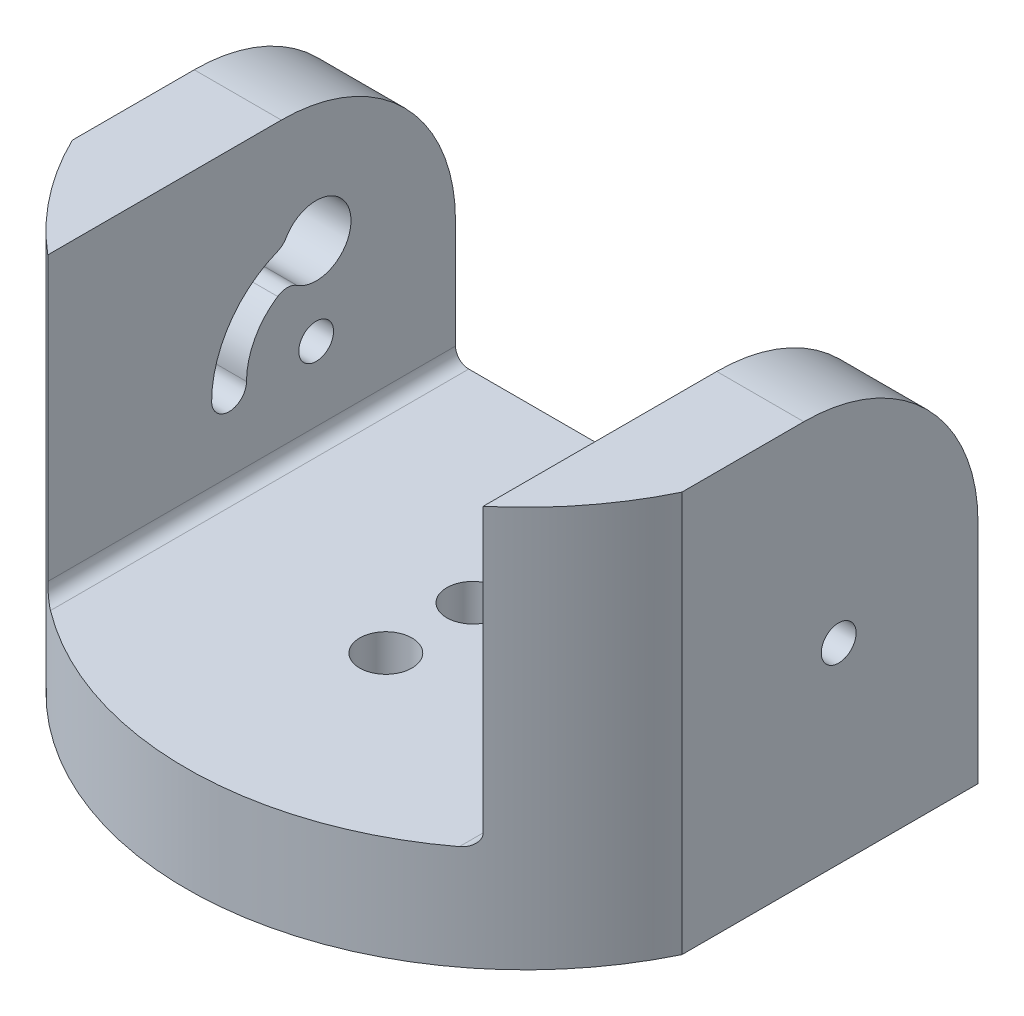
SolidWorks part; units mm, degrees
ref_plane "Front Plane" through (0, 0, 0) normal (0, 0, 1) x (1, 0, 0)
ref_plane "Top Plane" through (0, 0, 0) normal (0, 1, 0) x (1, 0, 0)
ref_plane "Right Plane" through (0, 0, 0) normal (1, 0, 0) x (0, 0, -1)
sketch "Sketch1" plane through (0, 0, 0) normal (0, 1, 0) x (1, 0, 0)
  line L1 (-17.5, -22.5) -> (17.5, -22.5)
  line L2 (-17.5, -22.5) -> (-17.5, 22.5)
  line L3 (-17.5, 22.5) -> (17.5, 22.5)
  line L4 (17.5, -22.5) -> (17.5, 22.5)
  line L5 (-17.5, -22.5) -> (17.5, 22.5) construction
  line L6 (-17.5, 22.5) -> (17.5, -22.5) construction
  point P0 (0, 0)
  dimension "D1" = 35
  dimension "D2" = 45
extrude "Boss-Extrude1" add sketch "Sketch1" along normal blind 6
sketch "Sketch2" plane through (-17.5, 0, 0) normal (-1, 0, 0) x (0, 0, 1)
  line L0 (-22.5, 6) -> (-22.5, 23)
  line L1 (-22.5, 23) -> (22.5, 23)
  line L2 (22.5, 23) -> (22.5, 6)
  line L3 (22.5, 6) -> (22.5, 0) construction
  line L4 (-22.5, 6) -> (22.5, 6) construction
  line L5 (-22.5, 6) -> (22.5, 6)
  dimension "D1" = 17
extrude "Boss-Extrude2" add sketch "Sketch2" against normal blind 5
mirror "Mirror1" about plane through (0, 0, 0) normal (1, 0, 0) of "Boss-Extrude2"
sketch "Sketch3" plane through (-12.5, 0, 0) normal (1, 0, 0) x (0, 0, -1)
  line L0 (9.5, 11) -> (14.5, 11) construction
  line L3 (22.5, 6) -> (-22.5, 6) construction
  line L4 (22.5, 23) -> (22.5, 6) construction
  line L5 (14.5, 11) -> (14.5, 16) construction
  arc A0 (14.5, 16) -> (9.5, 11) centre (14.5, 11) ccw construction
  arc A1 (14.5, 17) -> (8.5, 11) centre (14.5, 11) ccw
  arc A2 (14.5, 15) -> (10.5, 11) centre (14.5, 11) ccw
  arc A3 (14.5, 15) -> (14.5, 17) centre (14.5, 16) ccw
  arc A4 (8.5, 11) -> (10.5, 11) centre (9.5, 11) ccw
  circle A5 centre (14.5, 11) radius 1
  point P3 (10.9645, 14.5355)
  dimension "D1" = 1
  dimension "D6" = 2
  dimension "D2" = 5
  dimension "D3" = 5
  dimension "D5" = 8
extrude "Cut-Extrude1" cut sketch "Sketch3" against normal up to surface (5 mm away) up to face at (-17.5, 11.5, 0)
extrude "Cut-Extrude2" cut sketch "Sketch3<2>" along normal up to surface (30 mm away) contours A5 up to face at (17.5, 11.5, 0)
sketch "Sketch3<2>" plane through (-12.5, 0, 0) normal (1, 0, 0) x (0, 0, -1) same geometry as "Sketch3"
sketch "Sketch4" plane through (-17.5, 0, 0) normal (-1, 0, 0) x (0, 0, 1)
  circle A0 centre (-14.5, 16) radius 2
  dimension "D1" = 4
extrude "Cut-Extrude3" cut sketch "Sketch4" against normal up to surface (5 mm away) up to face at (-12.5, 11, -15.5)
fillet "Fillet1" radius 0.762 2 edges at (12.5, 6, 0) (-12.5, 6, 0)
fillet "Fillet2" radius 10 4 edges at (-15, 23, 22.5) (15, 23, 22.5) (15, 23, -22.5) (-15, 23, -22.5)
fillet "Fillet3" radius 1 2 edges at (-15, 14.7, -12.9801) (-15, 16.7, -12.6265)
sketch "Sketch5" plane through (0, 0, 0) normal (0, -1, 0) x (1, 0, 0)
  line L0 (17.5, 22.5) -> (17.5, -22.5) construction
  line L1 (-17.5, 22.5) -> (17.5, 22.5) construction
  line L2 (-17.5, -22.5) -> (-17.5, 22.5) construction
  line L3 (17.5, 22.5) -> (17.5, -5.5)
  line L4 (-17.5, 22.5) -> (17.5, 22.5)
  line L5 (-17.5, -5.5) -> (-17.5, 22.5)
  arc A0 (17.5, -5.5) -> (-17.5, -5.5) centre (0, -14) ccw
  dimension "D1" = 14
extrude "Cut-Extrude4" cut sketch "Sketch5" against normal up to surface (23 mm away) up to face at (-15, 23, 0)
sketch "Sketch6" plane through (0, 6, 0) normal (0, 1, 0) x (1, 0, 0)
  circle A0 centre (0, 11) radius 1.5
  circle A1 centre (0, 6) radius 1.5
  dimension "D1" = 3
  dimension "D2" = 5
  dimension "D3" = 6
extrude "Cut-Extrude5" cut sketch "Sketch6" against normal up to surface (6 mm away) up to face at (0, 0, -11.2612)
